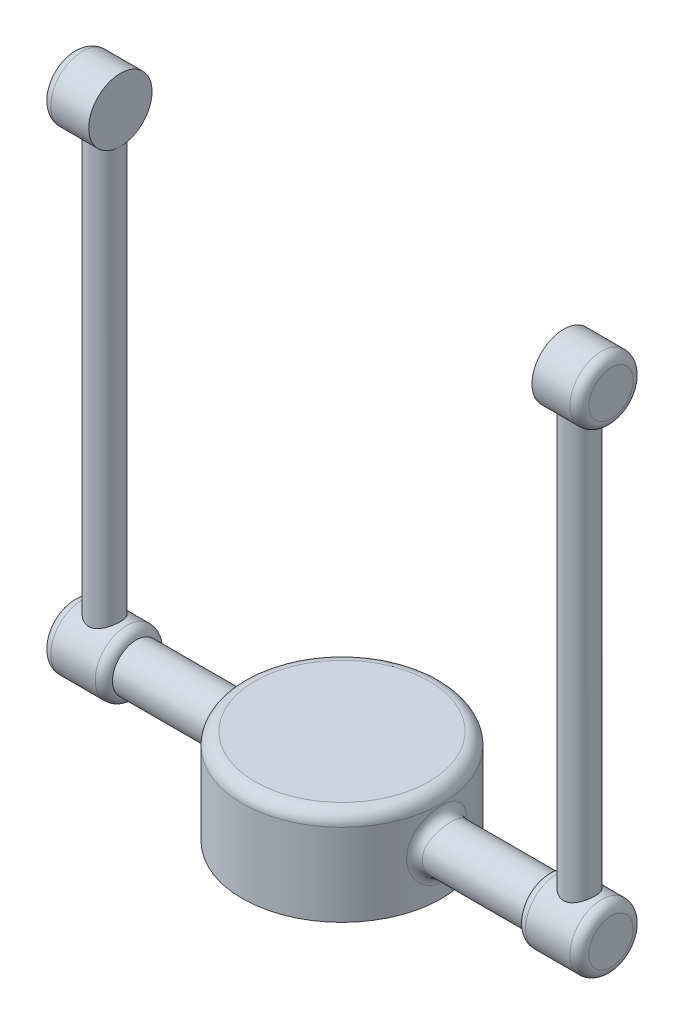
SolidWorks part; units mm, degrees
material "Polyester Resin"
ref_plane "Front Plane" through (0, 0, 0) normal (0, 0, 1) x (1, 0, 0)
ref_plane "Top Plane" through (0, 0, 0) normal (0, 1, 0) x (1, 0, 0)
ref_plane "Right Plane" through (0, 0, 0) normal (1, 0, 0) x (0, 0, -1)
sketch "Sketch1" plane through (0, 0, 0) normal (0, 1, 0) x (1, 0, 0)
  circle A0 centre (0, 0) radius 31.5
  dimension "D1" = 63
extrude "Boss-Extrude1" add sketch "Sketch1" along normal blind 30
sketch "Sketch2" plane through (0, 0, 0) normal (1, 0, 0) x (0, 0, -1)
  line L0 (0, 0) -> (0, 30) construction
  line L1 (31.5, 30) -> (-31.5, 30) construction
  circle A0 centre (0, 15) radius 7.5
  dimension "D1" = 15
extrude "Boss-Extrude2" add sketch "Sketch2" along normal blind 65
sketch "Sketch3" plane through (65, 0, 0) normal (1, 0, 0) x (0, 0, -1)
  circle A0 centre (0, 15) radius 10
  dimension "D1" = 20
extrude "Boss-Extrude3" add sketch "Sketch3" along normal blind 20
ref_axis "Axis1" through (0, 15, 0) along (1, 0, 0)
ref_plane "Plane1" through (0, 15, 0) normal (0, -1, 0) x (1, 0, 0)
sketch "Sketch4" plane through (0, 15, 0) normal (0, -1, 0) x (1, 0, 0)
  line L0 (0, 0) -> (65, 0) construction
  line L2 (65, 10) -> (65, -10) construction
  circle A0 centre (75, 0) radius 5
  dimension "D1" = 10
  dimension "D2" = 10
extrude "Boss-Extrude4" add sketch "Sketch4" against normal blind 150
sketch "Sketch5" plane through (85, 0, 0) normal (1, 0, 0) x (0, 0, -1)
  line L0 (0, 165) -> (0, 15) construction
  line L1 (5, 165) -> (-5, 165) construction
  circle A0 centre (0, 165) radius 10
  dimension "D1" = 20
extrude "Boss-Extrude5" add sketch "Sketch5" against normal blind 15
fillet "Fillet1" radius 3 4 edges at (30.6305, 16.492, -7.3501) (65, 15, -10) (85, 15, -10) (85, 165, -10)
mirror "Mirror1" about plane through (0, 0, 0) normal (1, 0, 0) of "Boss-Extrude5", "Boss-Extrude2", "Fillet1", "Boss-Extrude4", "Boss-Extrude3"
fillet "Fillet2" radius 4 1 edges at (0, 30, 31.5)
sketch "Sketch6" plane through (0, 0, 0) normal (0, -1, 0) x (1, 0, 0)
  circle A0 centre (0, 0) radius 29
  dimension "D1" = 58
extrude "Cut-Extrude1" cut sketch "Sketch6" against normal offset from surface (25 mm away) 5 up to face at (0, 30, 27.5)
chamfer "Chamfer1" distance 15 angle 45 1 edges at (0, 25, 29)
